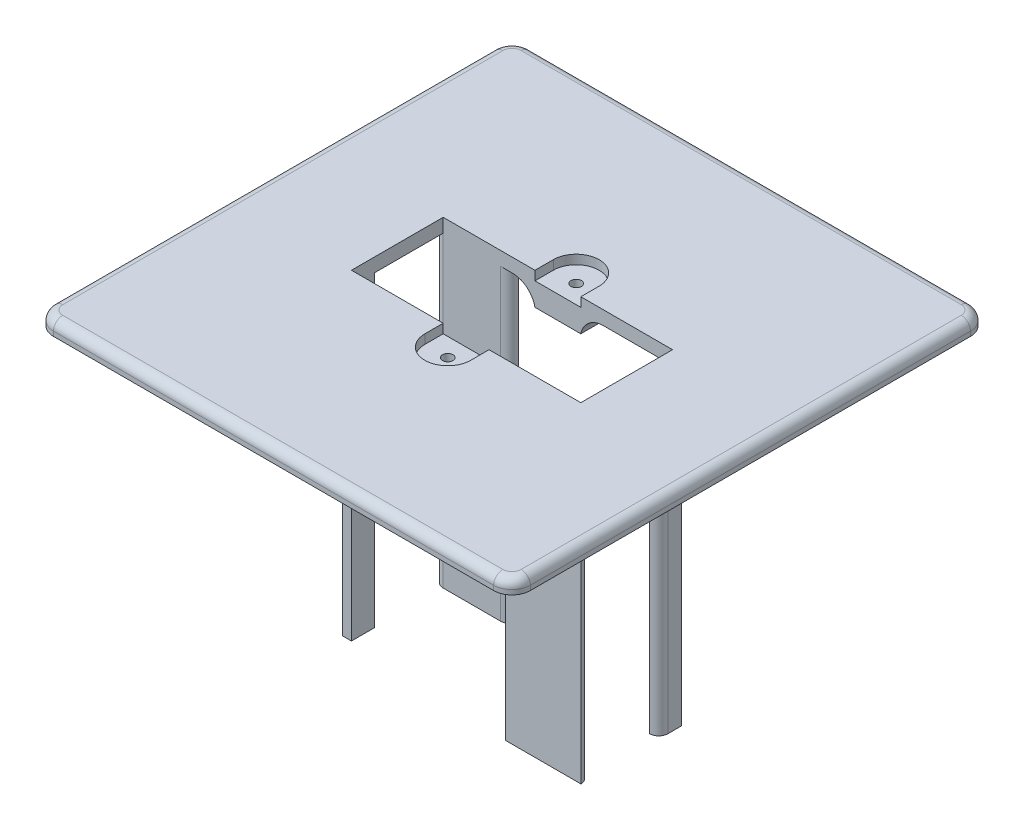
SolidWorks part; units mm, degrees
ref_plane "Front Plane" through (0, 0, 0) normal (0, 0, 1) x (1, 0, 0)
ref_plane "Top Plane" through (0, 0, 0) normal (0, 1, 0) x (1, 0, 0)
ref_plane "Right Plane" through (0, 0, 0) normal (1, 0, 0) x (0, 0, -1)
sketch "Sketch1" plane through (0, 0, 0) normal (0, 1, 0) x (1, 0, 0)
  line L0 (0, 51.97) -> (0, -51.97) construction
  line L1 (-10.975, 51.97) -> (10.975, 51.97) construction
  line L2 (-10.975, 51.97) -> (-10.975, 10.975) construction
  line L3 (-10.975, -51.97) -> (10.975, -51.97) construction
  line L4 (10.975, 51.97) -> (10.975, 10.975) construction
  line L5 (-10.975, 51.97) -> (10.975, -51.97) construction
  line L6 (-10.975, -51.97) -> (10.975, 51.97) construction
  line L7 (-51.97, 10.975) -> (-10.975, 10.975) construction
  line L8 (-51.97, 10.975) -> (-51.97, -10.975) construction
  line L9 (-51.97, -10.975) -> (-10.975, -10.975) construction
  line L10 (51.97, 10.975) -> (51.97, -10.975) construction
  line L11 (-51.97, 10.975) -> (51.97, -10.975) construction
  line L12 (-51.97, -10.975) -> (51.97, 10.975) construction
  line L13 (-51.97, 0) -> (51.97, 0) construction
  line L14 (10.975, -10.975) -> (51.97, -10.975) construction
  line L15 (10.975, -10.975) -> (10.975, -51.97) construction
  line L17 (10.975, 10.975) -> (51.97, 10.975) construction
  line L18 (-10.975, -10.975) -> (-10.975, -51.97) construction
  line L19 (51.97, 51.97) -> (-51.97, 51.97)
  line L20 (51.97, 51.97) -> (51.97, -51.97)
  line L21 (51.97, -51.97) -> (-51.97, -51.97)
  line L22 (-51.97, 51.97) -> (-51.97, -51.97)
  line L23 (51.97, 51.97) -> (-51.97, -51.97) construction
  line L24 (51.97, -51.97) -> (-51.97, 51.97) construction
  point P0 (0, 0)
  point P6 (0, 0)
  point P19 (0, 0)
  dimension "D1" = 21.95
  dimension "D2" = 103.94
extrude "Boss-Extrude1" add sketch "Sketch1" along normal blind 3
sketch "Sketch4" plane through (0, 0, 0) normal (0, -1, 0) x (1, 0, 0)
  line L0 (0, 14) -> (0, 10) construction
  line L1 (-5, 10) -> (5, 10) construction
  line L2 (-25, 5) -> (-25, -5) construction
  line L3 (25, 0) -> (-25, 0) construction
  line L4 (25, 5) -> (25, -5) construction
  line L5 (0, 10) -> (0, -10) construction
  line L6 (5, -10) -> (5, -14)
  line L7 (-5, -10) -> (-5, -14)
  line L8 (-5, 10) -> (-5, 14)
  line L9 (5, 10) -> (5, 14)
  line L10 (-5, 14) -> (5, 14) construction
  line L11 (-5, -10) -> (5, -10)
  line L12 (-5, 10) -> (5, 10)
  line L20 (-29, -5) -> (-25, -5) construction
  line L21 (-29, -5) -> (-29, 5) construction
  line L22 (-29, 5) -> (-25, 5) construction
  line L23 (-25, -5) -> (-25, 5) construction
  line L24 (29, -5) -> (25, -5) construction
  line L25 (29, -5) -> (29, 5) construction
  line L26 (29, 5) -> (25, 5) construction
  line L27 (25, -5) -> (25, 5) construction
  arc A0 (5, 14) -> (-5, 14) centre (0, 14) ccw
  arc A1 (-29, 5) -> (-29, -5) centre (-29, 0) ccw construction
  arc A2 (29, 5) -> (29, -5) centre (29, 0) cw construction
  circle A3 centre (0, -14) radius 1.1303
  circle A4 centre (0, 14) radius 1.1303
  circle A5 centre (-29, 0) radius 1.1303 construction
  circle A6 centre (29, 0) radius 1.1303 construction
  arc A7 (5, -14) -> (-5, -14) centre (0, -14) cw
  point P0 (0, 0)
  dimension "D5" = 2.2606
  dimension "D2" = 50
  dimension "D1" = 20
  dimension "D3" = 10
  dimension "D4" = 4
extrude "Boss-Extrude4" add sketch "Sketch4" along normal blind 4
fillet "Fillet2" radius 5 6 edges at (5, 0, 12) (-5, 0, 12) (-5, 0, -12) (5, 0, -12) (0, 0, 19) (0, 0, -19)
sketch "Sketch5" plane through (0, 0, 0) normal (0, -1, 0) x (1, 0, 0)
  line L1 (-25, 10) -> (25, 10)
  line L2 (-25, 10) -> (-25, -10)
  line L3 (-25, -10) -> (25, -10)
  line L4 (25, 10) -> (25, -10)
  line L5 (-25, 10) -> (25, -10) construction
  line L6 (-25, -10) -> (25, 10) construction
  line L7 (-5, 10) -> (5, 10) construction
  point P0 (0, 0)
  dimension "D1" = 50
extrude "Cut-Extrude1" cut sketch "Sketch5" against normal blind 10
sketch "Sketch9" plane through (0, 3, 0) normal (0, 1, 0) x (1, 0, 0)
  line L3 (-5, -10) -> (-5, -14)
  line L4 (5, -14) -> (5, -10)
  line L5 (5, -10) -> (-5, -10)
  line L6 (-5, -10) -> (-5, -14)
  line L7 (5, -14) -> (5, -10)
  line L8 (5, -10) -> (-5, -10)
  line L9 (-5, 14) -> (-5, 10)
  line L10 (5, 10) -> (5, 14)
  line L11 (-5, 10) -> (5, 10)
  line L12 (-5, 14) -> (-5, 10)
  line L13 (5, 10) -> (5, 14)
  line L14 (-5, 10) -> (5, 10)
  arc A3 (-5, -14) -> (5, -14) centre (0, -14) ccw
  arc A4 (-5, -14) -> (5, -14) centre (0, -14) ccw
  arc A5 (5, 14) -> (-5, 14) centre (0, 14) ccw
  arc A6 (5, 14) -> (-5, 14) centre (0, 14) ccw
  dimension "D2" = 0
  dimension "D3" = 0
extrude "Cut-Extrude3" cut sketch "Sketch9" against normal blind 2
sketch "Sketch10" plane through (0, 0, 0) normal (0, -1, 0) x (1, 0, 0)
  line L0 (-27, -10) -> (-25, -10)
  line L1 (-25, 0) -> (25, 0) construction
  line L2 (-25, 10) -> (-25, -10) construction
  line L3 (25, -10) -> (25, 10) construction
  line L4 (25, 10) -> (27, 10)
  line L5 (-25, 10) -> (-27, 10)
  line L7 (0, 10) -> (0, -10) construction
  line L8 (-5, 10) -> (5, 10) construction
  line L9 (5, -10) -> (-5, -10) construction
  line L10 (-25, 10) -> (-25, 5)
  line L11 (-25, 5) -> (-27, 5)
  line L12 (-27, 10) -> (-27, 5)
  line L16 (25, -10) -> (27, -10)
  line L17 (-25, -10) -> (-10.5, -10)
  line L18 (-27, -10) -> (-27, -11.97)
  line L19 (-27, -11.97) -> (-10.5, -11.97)
  line L20 (-10.5, -10) -> (-10.5, -11.97)
  line L21 (25, -10) -> (25, -5)
  line L22 (25, -5) -> (27, -5)
  line L23 (27, -10) -> (27, -5)
  line L26 (25, 10) -> (10.5, 10)
  line L27 (27, 10) -> (27, 11.97)
  line L28 (27, 11.97) -> (10.5, 11.97)
  line L29 (10.5, 10) -> (10.5, 11.97)
  line L30 (25, 0) -> (-25, 0) construction
  line L31 (-25, -5) -> (-27, -5) [skipped]
  line L32 (-25, -10) -> (-25, -5) [skipped]
  line L33 (-27, -10) -> (-27, -5) [skipped]
  line L34 (25, 10) -> (25, 5) [skipped]
  line L35 (27, 10) -> (27, 5) [skipped]
  line L36 (25, 5) -> (27, 5) [skipped]
  dimension "D1" = 2
  dimension "D2" = 10
  dimension "D3" = 5
  dimension "D4" = 1.97
  dimension "D5" = 16.5
  dimension "D6" = 2
extrude "Boss-Extrude7" add sketch "Sketch10" along normal blind 67
sketch "Sketch11" plane through (0, -4, 0) normal (0, -1, 0) x (1, 0, 0)
  circle A0 centre (0, -14) radius 1.1303 construction
  circle A1 centre (0, 14) radius 1.1303 construction
  circle A2 centre (0, -14) radius 1.1303
  circle A3 centre (0, 14) radius 1.1303
extrude "Cut-Extrude4" cut sketch "Sketch11" against normal blind 30
fillet "Fillet3" radius 2 4 edges at (0, 3, -51.97) (51.97, 3, 0) (0, 3, 51.97) (-51.97, 3, 0)
fillet "Fillet4" radius 2 6 edges at (-27, -33.5, 5) (27, -33.5, -5) (27, -33.5, 10) (-27, -33.5, -10) (-10.5, -33.5, -10) (10.5, -33.5, 10)
fillet "Fillet5" radius 4 8 edges at (51.3842, 2.4142, -51.3842) (51.3842, 2.4142, 51.3842) (-51.3842, 2.4142, 51.3842) (-51.3842, 2.4142, -51.3842) (-51.97, 0.5, -51.97) (-51.97, 0.5, 51.97) (51.97, 0.5, 51.97) (51.97, 0.5, -51.97)
